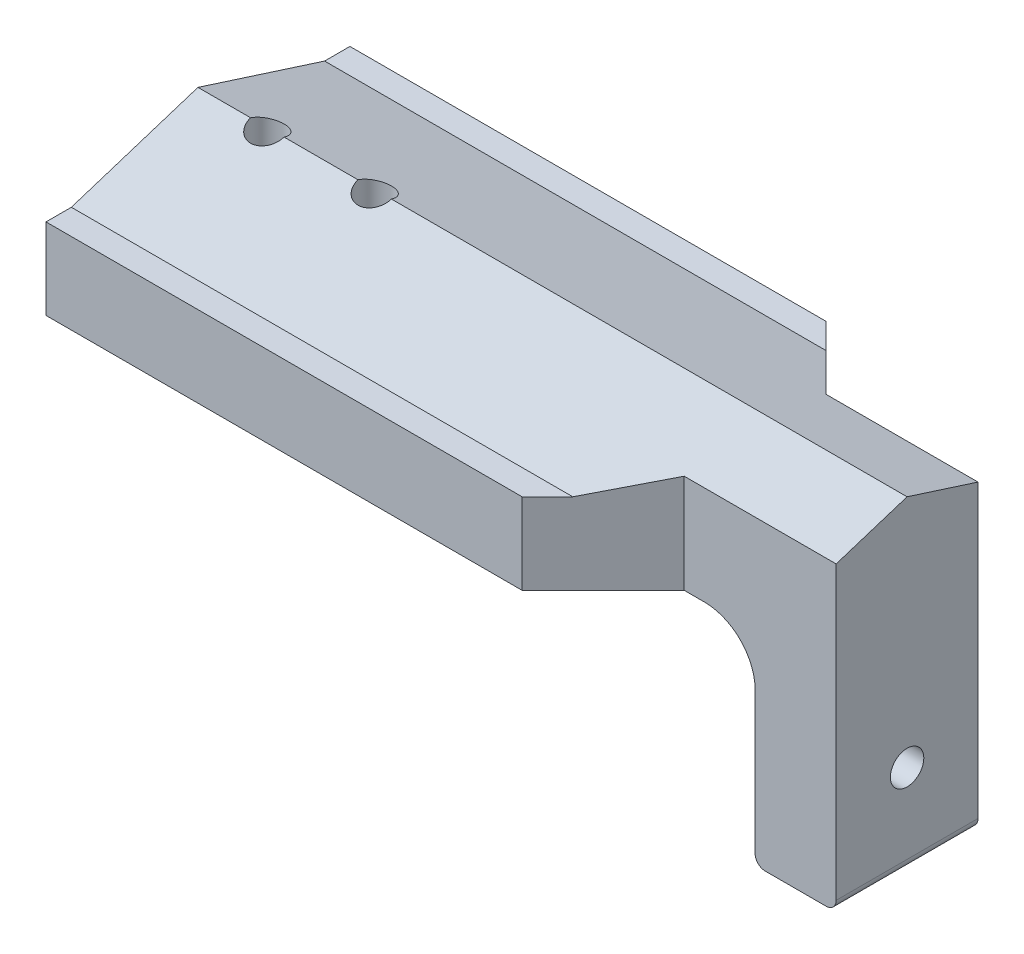
SolidWorks part; units mm, degrees
ref_plane "Front Plane" through (0, 0, 0) normal (0, 0, 1) x (1, 0, 0)
ref_plane "Top Plane" through (0, 0, 0) normal (0, 1, 0) x (1, 0, 0)
ref_plane "Right Plane" through (0, 0, 0) normal (1, 0, 0) x (0, 0, -1)
sketch "Sketch1" plane through (0, 0, 0) normal (1, 0, 0) x (0, 0, -1)
  line L0 (-12.5, 4) -> (12.5, 4)
  line L1 (-15, 4) -> (15, 4)
  line L2 (-15, 4) -> (-15, -4)
  line L3 (-15, -4) -> (15, -4)
  line L4 (15, 4) -> (15, -4)
  line L5 (-15, 4) -> (15, -4) construction
  line L6 (-15, -4) -> (15, 4) construction
  line L7 (0, 4) -> (0, 8) construction
  line L8 (0, 8) -> (12.5, 4)
  line L9 (0, 8) -> (-12.5, 4)
  point P0 (0, 0)
  point P9 (0, 4)
  dimension "D1" = 30
  dimension "D2" = 8
  dimension "D3" = 15
  dimension "D4" = 25
  dimension "D5" = 4
extrude "Boss-Extrude1" add sketch "Sketch1" along normal blind 70 contours L8 L9 L0 | L4 L1 L0 L2 L3 region at (0, 5.3333, 0) region at (0, 0, 0)
sketch "Sketch2" plane through (0, -4, 0) normal (0, -1, 0) x (1, 0, 0)
  line L0 (0, 0) -> (70, 0) construction
  line L1 (70, 15) -> (70, -15) construction
  line L2 (0, 15) -> (0, -15) construction
  line L3 (6.85, 3.2909) -> (4, 1.6454)
  line L4 (4, 1.6454) -> (4, -1.6454)
  line L5 (4, -1.6454) -> (6.85, -3.2909)
  line L6 (6.85, -3.2909) -> (9.7, -1.6454)
  line L7 (9.7, -1.6454) -> (9.7, 1.6454)
  line L8 (9.7, 1.6454) -> (6.85, 3.2909)
  line L10 (17.45, -3.2909) -> (20.3, -1.6454)
  line L11 (20.3, -1.6454) -> (20.3, 1.6454)
  line L12 (20.3, 1.6454) -> (17.45, 3.2909)
  line L13 (17.45, 3.2909) -> (14.6, 1.6454)
  line L14 (14.6, 1.6454) -> (14.6, -1.6454)
  line L15 (14.6, -1.6454) -> (17.45, -3.2909)
  circle A0 centre (6.85, 0) radius 1.65
  circle A1 centre (6.85, 0) radius 2.85 construction
  circle A2 centre (17.45, 0) radius 1.65
  circle A3 centre (17.45, 0) radius 2.85 construction
  dimension "D1" = 3.3
  dimension "D4" = 3.3
  dimension "D6" = 10.6
  dimension "D2" = 5.7
  dimension "D3" = 4
  dimension "D5" = 5.7
extrude "Cut-Extrude1" cut sketch "Sketch2" against normal blind 5
sketch "Sketch3" plane through (0, -4, 0) normal (0, -1, 0) x (1, 0, 0)
  circle A0 centre (6.85, 0) radius 1.65
  circle A1 centre (17.45, 0) radius 1.65
extrude "Cut-Extrude2" cut sketch "Sketch3" against normal blind 61
sketch "Sketch4" plane through (0, -4, 0) normal (0, -1, 0) x (1, 0, 0)
  line L0 (70, -15) -> (0, -15) construction
  line L1 (70, 15) -> (62, 15)
  line L2 (70, 15) -> (70, -15)
  line L3 (70, -15) -> (62, -15)
  line L4 (62, 15) -> (62, -15)
  dimension "D1" = 8
extrude "Boss-Extrude2" add sketch "Sketch4" along normal blind 20
sketch "Sketch5" plane through (62, 0, 0) normal (-1, 0, 0) x (0, 0, 1)
  line L0 (0, -24) -> (0, -4) construction
  line L1 (15, -24) -> (-15, -24) construction
  line L2 (15, -4) -> (-15, -4) construction
  line L4 (3.2909, -15.15) -> (1.6454, -12.3)
  line L5 (1.6454, -12.3) -> (-1.6454, -12.3)
  line L6 (-1.6454, -12.3) -> (-3.2909, -15.15)
  line L7 (-3.2909, -15.15) -> (-1.6454, -18)
  line L8 (-1.6454, -18) -> (1.6454, -18)
  line L9 (1.6454, -18) -> (3.2909, -15.15)
  circle A0 centre (0, -15.15) radius 1.65
  circle A1 centre (0, -15.15) radius 2.85 construction
  dimension "D1" = 3.3
  dimension "D2" = 5.7
  dimension "D3" = 6
extrude "Cut-Extrude3" cut sketch "Sketch5" against normal blind 4 contours L4 L5 L6 L7 L8 L9 | A0
sketch "Sketch6" plane through (62, 0, 0) normal (-1, 0, 0) x (0, 0, 1)
  circle A0 centre (0, -15.15) radius 1.65
extrude "Cut-Extrude4" cut sketch "Sketch6" against normal blind 40
fillet "Fillet1" radius 1 2 edges at (70, -24, 0) (62, -24, 0)
fillet "Fillet2" radius 5 1 edges at (62, -4, 0)
sketch "Sketch7" plane through (0, -24, 0) normal (0, -1, 0) x (1, 0, 0)
  line L0 (70, 0) -> (17.45, 0) construction
  line L1 (70, 15) -> (70, -15) construction
  line L2 (57, -15) -> (57, 15) construction
  line L3 (70, 15) -> (57, 15)
  line L4 (70, 15) -> (70, 7)
  line L5 (70, 7) -> (57, 7)
  line L6 (57, 15) -> (57, 7)
  line L8 (57, -15) -> (70, -15)
  line L9 (57, -15) -> (57, -7)
  line L10 (57, -7) -> (70, -7)
  line L11 (70, -15) -> (70, -7)
  line L14 (57, 7) -> (57, 15)
  line M7 (63, -15) -> (69, -15)
  line M8 (69, -15) -> (69, 15)
  line M9 (69, 15) -> (63, 15)
  line M10 (63, 15) -> (63, -15)
  dimension "D1" = 8
  dimension "D2" = 8
extrude "Cut-Extrude5" cut sketch "Sketch7" against normal blind 42 contours L5 M8 M9 M10 | L5 L4 L3 M8 | L3 L6 L5 M10 | L10 L9 L8 M10 | L10 M10 M7 M8 | L8 L11 L10 M8 region at (69.5, -24, 11) region at (66, -24, 11) region at (60, -24, 11) region at (66, -24, -11) region at (69.5, -24, -11) region at (60, -24, -11)
chamfer "Chamfer1" distance 10 angle 45 2 edges at (57, 0, 15) (57, 0, -15)
